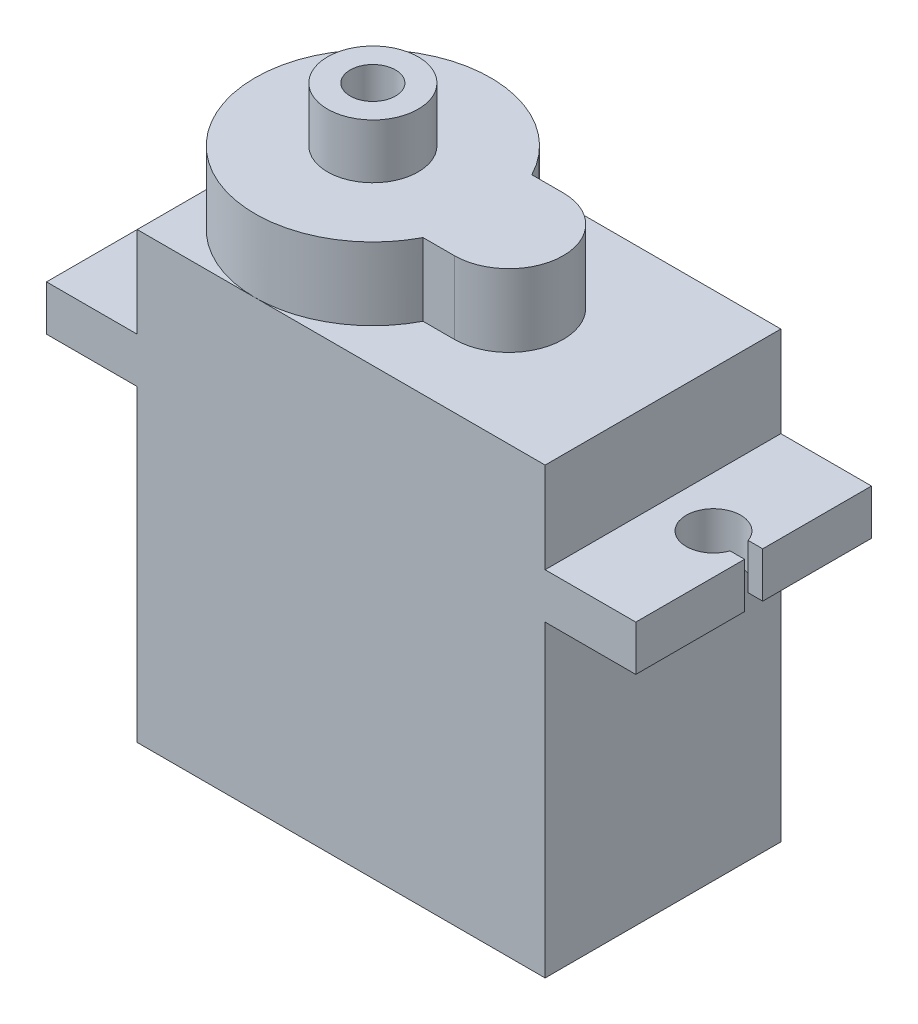
SolidWorks part; units mm, degrees
ref_plane "Front Plane" through (0, 0, 0) normal (0, 0, 1) x (1, 0, 0)
ref_plane "Top Plane" through (0, 0, 0) normal (0, 1, 0) x (1, 0, 0)
ref_plane "Right Plane" through (0, 0, 0) normal (1, 0, 0) x (0, 0, -1)
sketch "Sketch1" plane through (0, 0, 0) normal (0, 0, 1) x (1, 0, 0)
  line L0 (-11.25, -8.5) -> (11.25, -8.5)
  line L1 (11.25, -8.5) -> (11.25, 8.5)
  line L2 (11.25, 8.5) -> (16.25, 8.5)
  line L3 (16.25, 8.5) -> (16.25, 11)
  line L4 (16.25, 11) -> (11.25, 11)
  line L5 (11.25, 11) -> (11.25, 16)
  line L6 (11.25, 16) -> (-11.25, 16)
  line L7 (-11.25, 16) -> (-11.25, 11)
  line L8 (-11.25, 11) -> (-16.25, 11)
  line L9 (-16.25, 11) -> (-16.25, 8.5)
  line L10 (-16.25, 8.5) -> (-11.25, 8.5)
  line L11 (-11.25, 8.5) -> (-11.25, -8.5)
  dimension "D1" = 22.5
  dimension "D2" = 17
  dimension "D3" = 17
  dimension "D4" = 2.5
  dimension "D5" = 5
  dimension "D6" = 5
  dimension "D7" = 2.5
  dimension "D8" = 5
  dimension "D9" = 11.25
  dimension "D10" = 8.5
extrude "Boss-Extrude1" add sketch "Sketch1" along normal blind 6.5 and the other way blind 6.5
sketch "Sketch3" plane through (0, 16, 0) normal (0, 1, 0) x (1, 0, 0)
  line L0 (11.25, 6.5) -> (-11.25, 6.5) construction
  line L1 (-11.25, 6.5) -> (-11.25, -6.5) construction
  line L2 (-4.75, 0) -> (2.75, 0) construction
  line L3 (-4.75, 3) -> (2.75, 3)
  line L4 (-4.75, -3) -> (2.75, -3)
  circle A0 centre (-4.75, 0) radius 6.5
  arc A1 (-4.75, 3) -> (-4.75, -3) centre (-4.75, 0) ccw
  arc A2 (2.75, -3) -> (2.75, 3) centre (2.75, 0) ccw
  point P4 (-1, 0)
  dimension "D1" = 3
  dimension "D2" = 7.5
extrude "Boss-Extrude2" add sketch "Sketch3" along normal blind 4 contours A1 L3 A0 L4 | L3 A1 L4 A0 | L4 A2 L3 A0 region at (-7.9287, 16, 0) region at (-2.8208, 16, 0) region at (3.3645, 16, 0)
sketch "Sketch4" plane through (0, 20, 0) normal (0, 1, 0) x (1, 0, 0)
  circle A0 centre (-4.75, 0) radius 2.5
  arc A1 (-4.75, 6.5) -> (-11.25, 0) centre (-4.75, 0) ccw construction
  circle A2 centre (-4.75, 0) radius 1.25
  dimension "D1" = 0
  dimension "D2" = 5
  dimension "D3" = 2.5
extrude "Boss-Extrude3" add sketch "Sketch4" along normal blind 3
sketch "Sketch5" plane through (0, 0, 0) normal (0, 1, 0) x (1, 0, 0)
  line L0 (-16.25, 6.5) -> (-16.25, -6.5) construction
  line L1 (-16.25, 0.5) -> (-15.45, 0.5)
  line L2 (-16.25, 0.5) -> (-16.25, -0.5)
  line L3 (-16.25, -0.5) -> (-15.45, -0.5)
  line L5 (0, 0) -> (0, -2.9438) construction
  line L6 (16.25, -0.5) -> (15.45, -0.5)
  line L7 (16.25, 0.5) -> (16.25, -0.5)
  line L8 (16.25, 0.5) -> (15.45, 0.5)
  arc A0 (-15.45, -0.5) -> (-15.45, 0.5) centre (-14.0358, 0) ccw
  arc A1 (15.45, -0.5) -> (15.45, 0.5) centre (14.0358, 0) cw
  dimension "D4" = 3
  dimension "D1" = 0.5
  dimension "D2" = 0.5
  dimension "D3" = 0.8
extrude "Cut-Extrude1" cut sketch "Sketch5" against normal through all both and the other way through all
